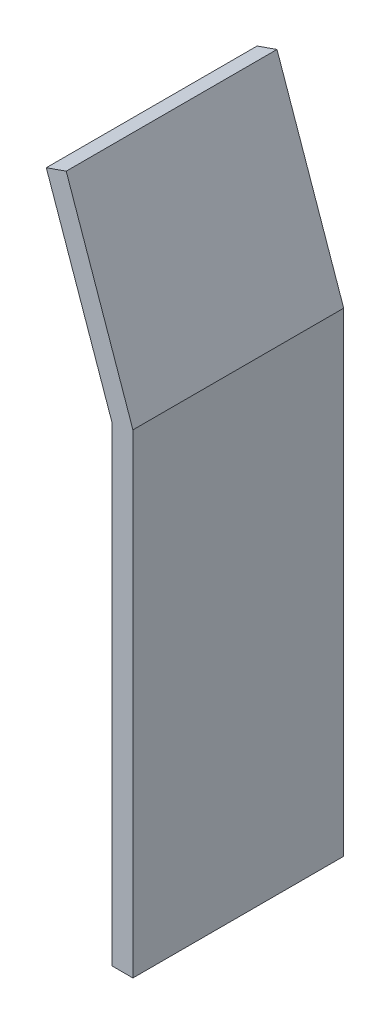
SolidWorks part; units mm, degrees
ref_plane "Front" through (0, 0, 0) normal (0, 0, 1) x (1, 0, 0)
ref_plane "Top" through (0, 0, 0) normal (0, 1, 0) x (1, 0, 0)
ref_plane "Right" through (0, 0, 0) normal (1, 0, 0) x (0, 0, -1)
sketch "Sketch1" plane through (0, 0, 0) normal (0, 0, 1) x (1, 0, 0)
  line L0 (0, 0) -> (0, -447)
  line L1 (0, -447) -> (20, -447)
  line L2 (20, -447) -> (20, 3.3971)
  line L4 (-43.2922, 184.3337) -> (-62.1705, 177.73)
  line L5 (-62.1705, 177.73) -> (0, 0)
  line L6 (-43.2922, 184.3337) -> (20, 3.3971)
  dimension "D1" = 20
  dimension "D2" = 20
  dimension "D3" = 447
  dimension "D4" = 188.29
  dimension "D5" = 160.72
  dimension "D6" = 191.6871
extrude "Boss-Extrude1" add sketch "Sketch1" along normal blind 200
